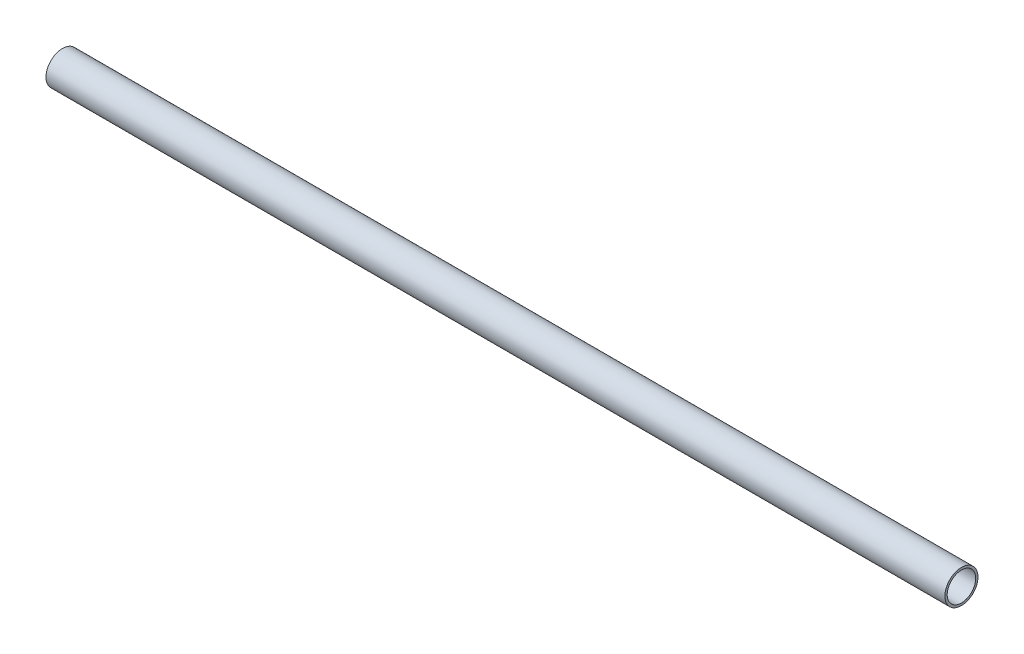
SolidWorks part; units mm, degrees
ref_plane "Front Plane" through (0, 0, 0) normal (0, 0, 1) x (1, 0, 0)
ref_plane "Top Plane" through (0, 0, 0) normal (0, 1, 0) x (1, 0, 0)
ref_plane "Right Plane" through (0, 0, 0) normal (1, 0, 0) x (0, 0, -1)
ref_axis "Axis1" through (-88.99, 0, 0) along (1, 0, 0)
sketch "Sketch1" plane through (0, 0, 0) normal (1, 0, 0) x (0, 0, -1)
  circle A0 centre (0, 0) radius 0.635
  circle A1 centre (0, 0) radius 0.7366
  dimension "D1" = 1.4732
  dimension "D2" = 1.27
extrude "Boss-Extrude1" add sketch "Sketch1" along normal blind 40
